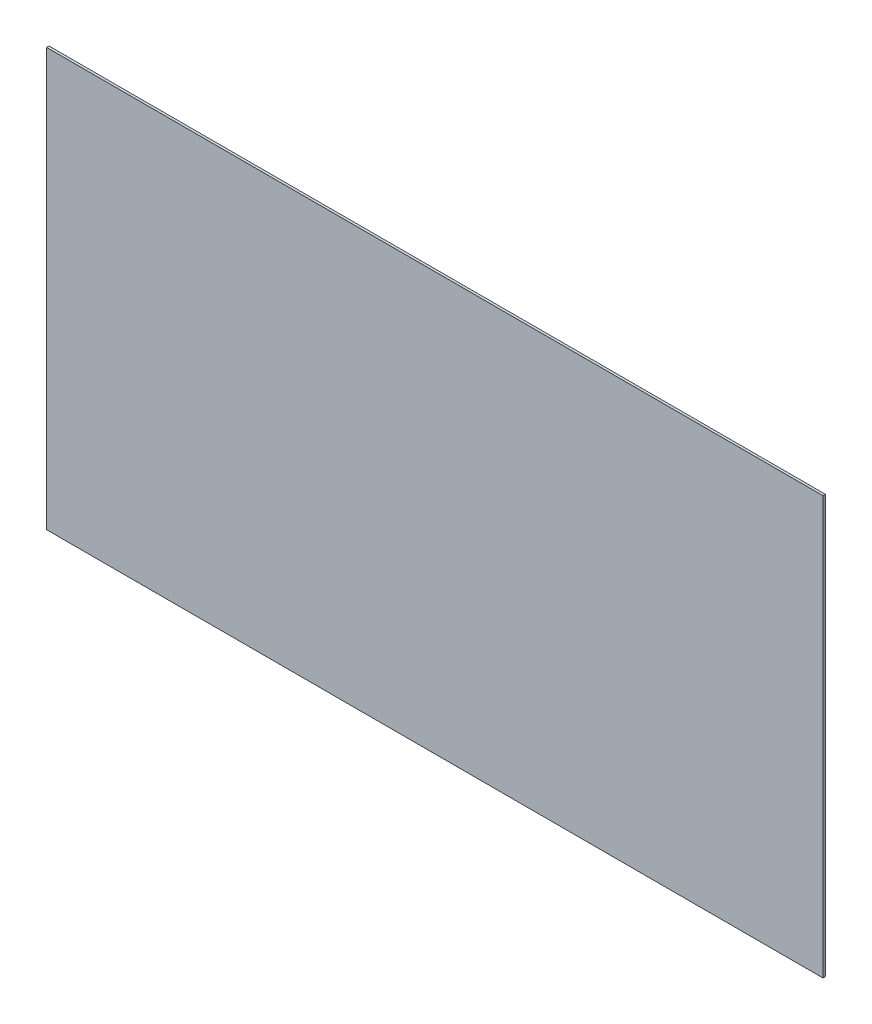
SolidWorks part; units mm, degrees
material "Pine"
ref_plane "Front Plane" through (0, 0, 0) normal (0, 0, 1) x (1, 0, 0)
ref_plane "Top Plane" through (0, 0, 0) normal (0, 1, 0) x (1, 0, 0)
ref_plane "Right Plane" through (0, 0, 0) normal (1, 0, 0) x (0, 0, -1)
sketch "Sketch1" plane through (0, 0, 0) normal (0, 0, 1) x (1, 0, 0)
  line L1 (0, 0) -> (1003.3, 0)
  line L2 (0, 0) -> (0, 539.75)
  line L3 (0, 539.75) -> (1003.3, 539.75)
  line L4 (1003.3, 0) -> (1003.3, 539.75)
  dimension "D1" = 539.75
  dimension "D2" = 1003.3
extrude "Boss-Extrude1" add sketch "Sketch1" along normal blind 3.175
